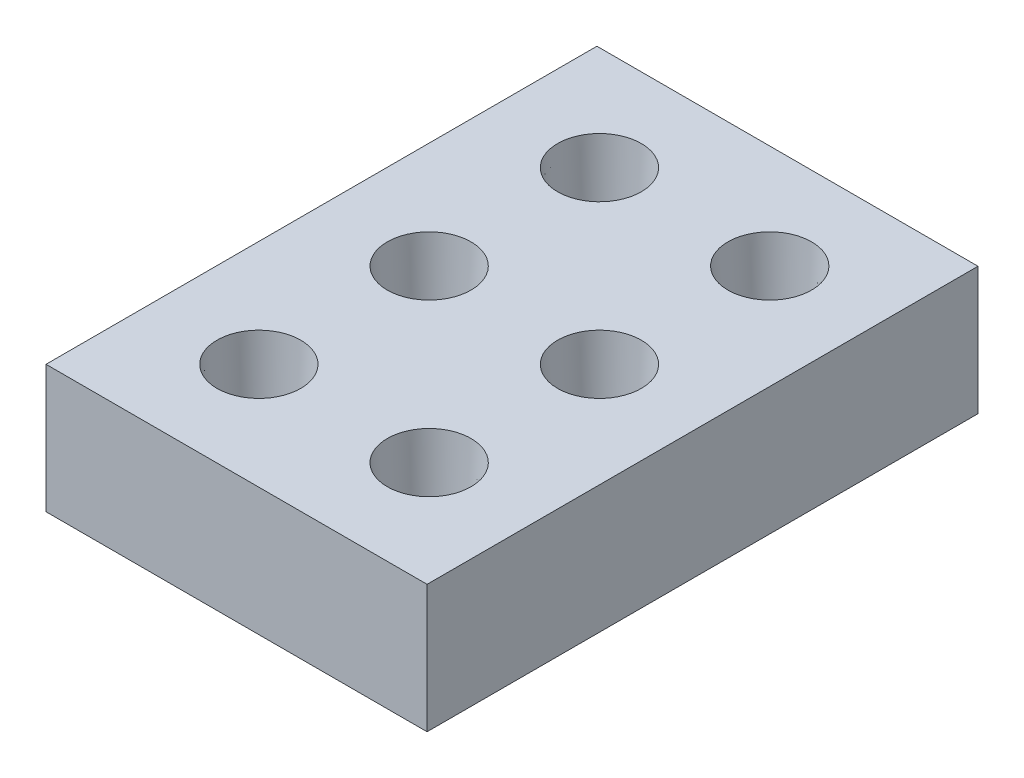
SolidWorks part; units mm, degrees
ref_plane "Front Plane" through (0, 0, 0) normal (0, 0, 1) x (1, 0, 0)
ref_plane "Top Plane" through (0, 0, 0) normal (0, 1, 0) x (1, 0, 0)
ref_plane "Right Plane" through (0, 0, 0) normal (1, 0, 0) x (0, 0, -1)
sketch "Sketch1" plane through (0, 0, 0) normal (0, 1, 0) x (1, 0, 0)
  line L0 (-5, 0) -> (12.9024, 0)
  line L1 (-5, 0) -> (-5, 25.8806)
  line L2 (-5, 25.8806) -> (12.9024, 25.8806)
  line L3 (12.9024, 0) -> (12.9024, 25.8806)
  dimension "D1" = 17.9024
  dimension "D2" = 25.8806
  dimension "D3" = 5
extrude "Boss-Extrude1" add sketch "Sketch1" along normal blind 6
sketch "Sketch3" plane through (0, 0, 0) normal (-1, 0, 0) x (0, 0, 1)
  line L0 (-5, 6) -> (-5, 0)
  line L1 (-25.8806, 6) -> (0, 6) construction
  line L2 (-25.8806, 0) -> (0, 0) construction
  line L3 (-5, 0) -> (-6.77, 0)
  line L4 (-6.77, 0) -> (-6.77, 3.2)
  line L5 (-6.77, 3.2) -> (-6.9658, 6)
  line L6 (-6.9658, 6) -> (-5, 6)
  line L7 (0, 6) -> (0, 0) construction
  dimension "D1" = 1.77
  dimension "D2" = 2.8
  dimension "D3" = 176
  dimension "D4" = 5
  dimension "D5" = 1.9658
revolve "Cut-Revolve1" cut sketch "Sketch3" angle 360 about L0
pattern_linear "LPattern1" count 3 spacing 8 along (0, 0, -1) count 2 spacing 8 along (1, 0, 0) of "Cut-Revolve1"
